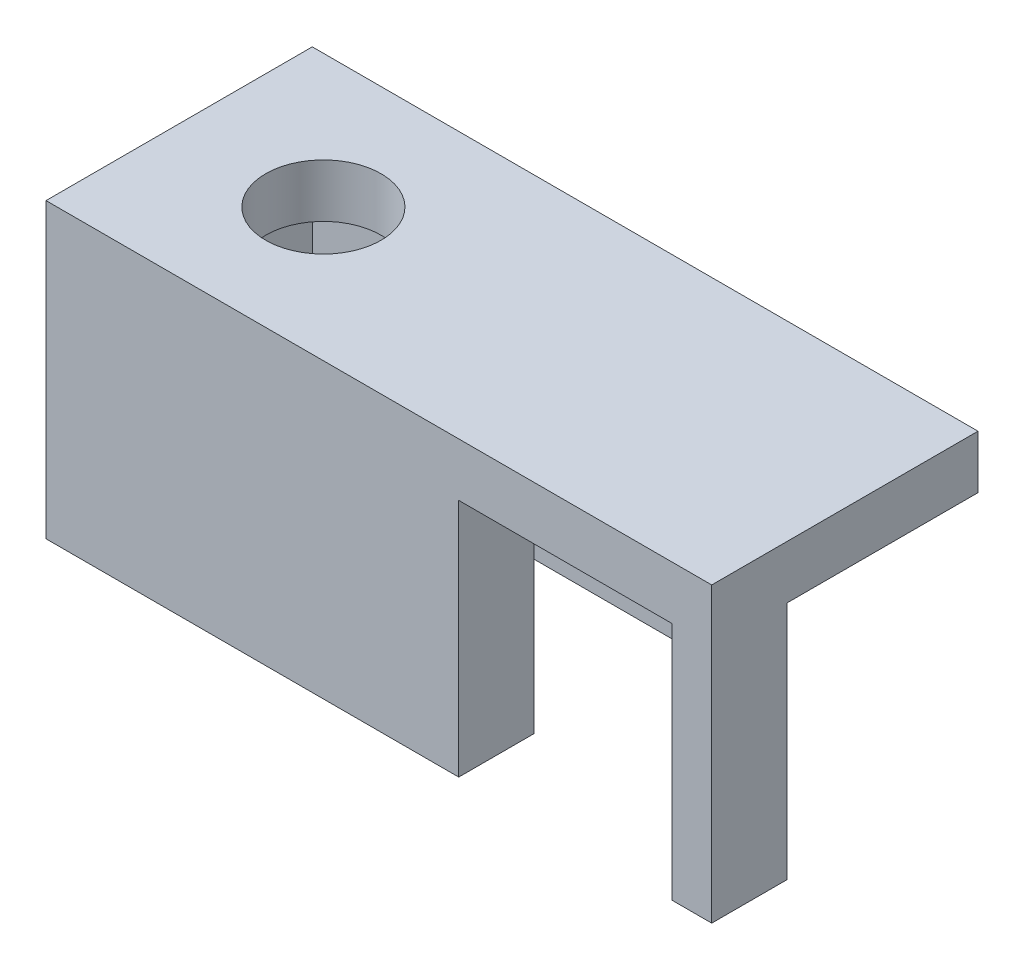
SolidWorks part; units mm, degrees
ref_plane "Front Plane" through (0, 0, 0) normal (0, 0, 1) x (1, 0, 0)
ref_plane "Top Plane" through (0, 0, 0) normal (0, 1, 0) x (1, 0, 0)
ref_plane "Right Plane" through (0, 0, 0) normal (1, 0, 0) x (0, 0, -1)
sketch "Sketch1" plane through (0, -4.342, 0) normal (0, -1, 0) x (1, 0, 0)
  line L0 (-40.9843, 28.2004) -> (-18.4843, 28.2004) construction
  line L1 (-11.5696, 28.2004) -> (-86.5696, 28.2004)
  line L2 (-11.5696, 28.2004) -> (-11.5696, -1.7996)
  line L3 (-11.5696, -1.7996) -> (-86.5696, -1.7996)
  line L4 (-86.5696, 28.2004) -> (-86.5696, -1.7996)
  dimension "D1" = 75
  dimension "D2" = 30
extrude "Boss-Extrude1" add sketch "Sketch1" along normal blind 6 contours L1 L4 L3 L2
sketch "Sketch2" plane through (0, -10.342, 0) normal (0, -1, 0) x (-1, 0, 0)
  line L1 (86.5696, 1.7996) -> (38.5696, 1.7996)
  line L2 (86.5696, 1.7996) -> (86.5696, -2.7004)
  line L3 (86.5696, -2.7004) -> (38.5696, -2.7004)
  line L4 (38.5696, 1.7996) -> (38.5696, -2.7004)
  line L5 (38.5696, 1.7996) -> (43.5696, 1.7996)
  line L6 (38.5696, 1.7996) -> (38.5696, -7.2004)
  line L7 (38.5696, -7.2004) -> (43.5696, -7.2004)
  line L8 (43.5696, 1.7996) -> (43.5696, -7.2004)
  line L9 (11.5696, -28.2004) -> (86.5696, -28.2004) construction
  line L10 (86.5696, 1.7996) -> (82.0696, 1.7996)
  line L11 (86.5696, 1.7996) -> (86.5696, -28.2004)
  line L12 (86.5696, -28.2004) -> (82.0696, -28.2004)
  line L13 (82.0696, 1.7996) -> (82.0696, -28.2004)
  line L14 (11.5696, -28.2004) -> (11.5696, 1.7996) construction
  line L15 (86.5696, -28.2004) -> (40.0696, -28.2004)
  line L16 (86.5696, -28.2004) -> (86.5696, -23.7004)
  line L17 (86.5696, -23.7004) -> (40.0696, -23.7004)
  line L18 (40.0696, -28.2004) -> (40.0696, -23.7004)
  line L19 (46.0696, -28.2004) -> (40.0696, -28.2004)
  line L20 (46.0696, -28.2004) -> (46.0696, -19.7004)
  line L21 (46.0696, -19.7004) -> (40.0696, -19.7004)
  line L22 (40.0696, -28.2004) -> (40.0696, -19.7004)
  line L24 (11.5696, -28.2004) -> (16.0696, -28.2004)
  line L25 (11.5696, -28.2004) -> (11.5696, -19.7004)
  line L26 (11.5696, -19.7004) -> (16.0696, -19.7004)
  line L27 (16.0696, -28.2004) -> (16.0696, -19.7004)
  dimension "D1" = 4.5
  dimension "D2" = 48
  dimension "D3" = 5
  dimension "D4" = 9
  dimension "D5" = 4.5
  dimension "D6" = 4.5
  dimension "D7" = 0
  dimension "D8" = 28.5
  dimension "D9" = 40.5
  dimension "D10" = 8.5
  dimension "D11" = 8.5
  dimension "D12" = 4.5
extrude "Boss-Extrude4" add sketch "Sketch2" along normal blind 27 contours L16 L15 L18 L17 | L2 L1 L4 L3 | L11 L10 L13 L12 | L6 L5 L8 L7 | L20 L19 L22 L21 | L25 L24 L27 L26
sketch "Sketch7" plane through (-38.5696, 0, 0) normal (1, 0, 0) x (0, 0, -1)
  line L1 (-7.2004, -37.342) -> (-2.7004, -37.342)
  line L2 (-7.2004, -37.342) -> (-7.2004, -22.342)
  line L3 (-7.2004, -22.342) -> (-2.7004, -22.342)
  line L4 (-2.7004, -37.342) -> (-2.7004, -22.342)
  dimension "D1" = 15
  dimension "D2" = 4.5
extrude "Cut-Extrude1" cut sketch "Sketch7" against normal blind 6
sketch "Sketch9" plane through (0, -4.342, 0) normal (0, 1, 0) x (1, 0, 0)
  line L1 (-86.5696, -28.2004) -> (-86.5696, 1.7996) construction
  line L2 (-11.5696, 1.7996) -> (-86.5696, 1.7996) construction
  circle A0 centre (-70.3196, -13.2004) radius 6.5
  dimension "D1" = 16.25
  dimension "D2" = 15
  dimension "D3" = 13
extrude "Cut-Extrude2" cut sketch "Sketch9" against normal blind 30
